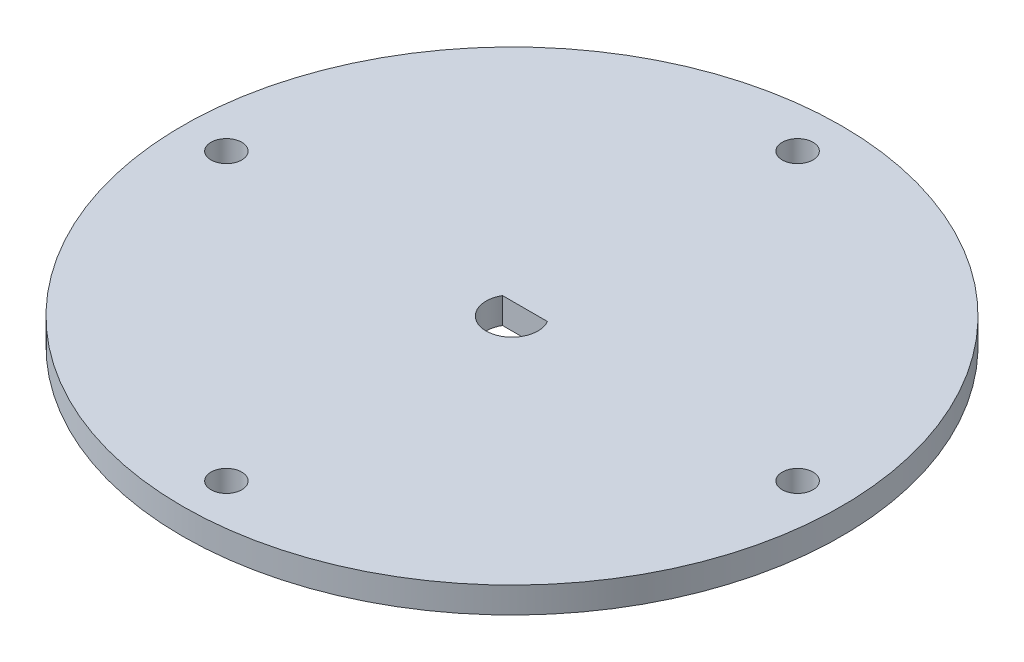
SolidWorks part; units mm, degrees
ref_plane "Front Plane" through (0, 0, 0) normal (0, 0, 1) x (1, 0, 0)
ref_plane "Top Plane" through (0, 0, 0) normal (0, 1, 0) x (1, 0, 0)
ref_plane "Right Plane" through (0, 0, 0) normal (1, 0, 0) x (0, 0, -1)
sketch "Sketch1" plane through (0, 0, 0) normal (0, 1, 0) x (1, 0, 0)
  circle A0 centre (0, 0) radius 38.1
  dimension "D1" = 76.2
extrude "Boss-Extrude1" add sketch "Sketch1" along normal blind 3
sketch "Sketch3" plane through (0, 3, 0) normal (0, 1, 0) x (1, 0, 0)
  line L0 (0, 0) -> (33.02, 0) construction
  circle A0 centre (33.02, 0) radius 1.778
  dimension "D1" = 3.556
  dimension "D2" = 33.02
extrude "Cut-Extrude1" cut sketch "Sketch3" against normal through all
pattern_circular "CirPattern1" count 4 over 360 about axis through (0, 3, 0) along (0, -1, 0) of "Cut-Extrude1"
sketch "Sketch4" plane through (0, 3, 0) normal (0, 1, 0) x (1, 0, 0)
  line L0 (-2.5981, 1.5) -> (2.5981, 1.5)
  arc A0 (-2.5981, 1.5) -> (2.5981, 1.5) centre (0, 0) ccw
  dimension "D1" = 6
  dimension "D2" = 1.5
extrude "Cut-Extrude2" cut sketch "Sketch4" against normal through all
